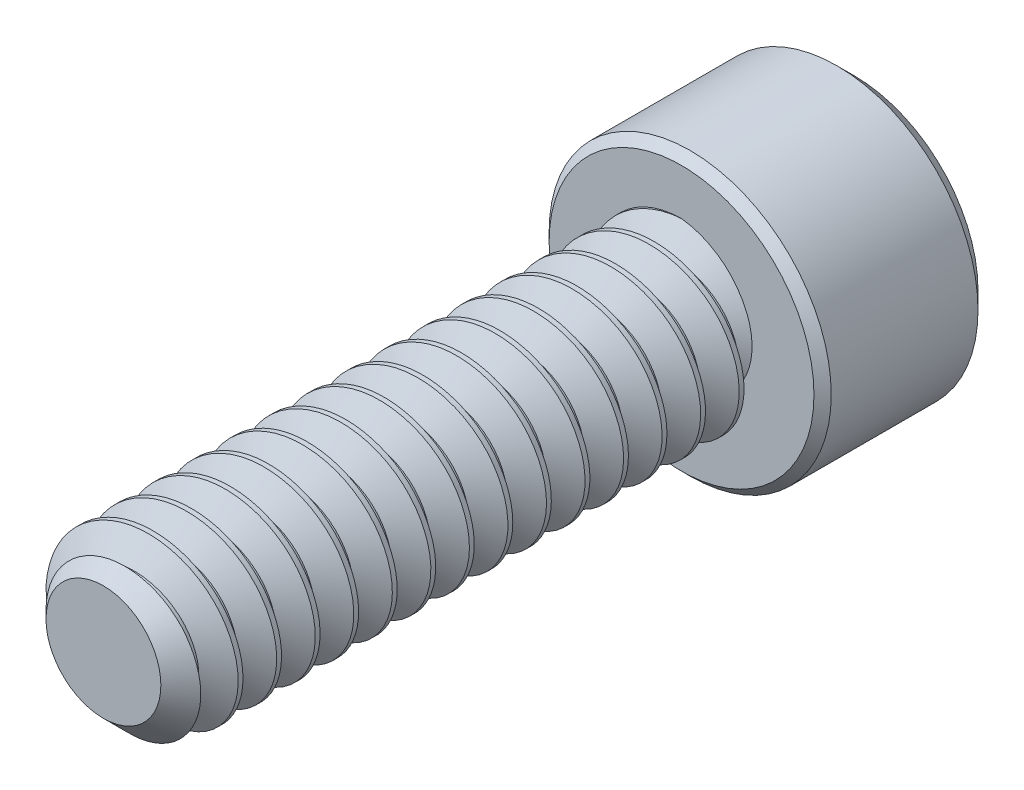
SolidWorks part; units mm, degrees
material "Plain Carbon Steel"
ref_plane "Front Plane" through (0, 0, 0) normal (0, 0, 1) x (1, 0, 0)
ref_plane "Top Plane" through (0, 0, 0) normal (0, 1, 0) x (1, 0, 0)
ref_plane "Right Plane" through (0, 0, 0) normal (1, 0, 0) x (0, 0, -1)
sketch "Sketch1" plane through (0, 0, 0) normal (0, 0, 1) x (1, 0, 0)
  line L0 (0, 1.4224) -> (0, -1.4224) construction
  circle A0 centre (0, 0) radius 1.4224
  dimension "OD" = 2.8448
extrude "Extrude1" add sketch "Sketch1" against normal blind 9.525
sketch "Sketch2" plane through (0, 0, 0) normal (0, 0, 1) x (1, 0, 0)
  circle A0 centre (0, 0) radius 1.4224 construction
  circle A1 centre (0, 0) radius 1.4224
curve "Helix/Spiral1" pitch 0.635 height 10.16 radius 1.4224 centre (0, 0, 0) axis (0, 0, -1) start towards (0, 1, 0) parameters "pitch"=0.635
chamfer "Chamfer3" distance 0.4763 angle 45 1 edges at (1.4224, 0, 0)
sketch "Sketch3" plane through (0, 0, 0) normal (1, 0, 0) x (0, 0, -1)
  line L0 (-0.5556, 1.4224) -> (-0.3175, 1.01)
  line L1 (-0.3175, 1.01) -> (-0.2381, 1.01)
  line L2 (-0.2381, 1.01) -> (0, 1.4224)
  line L3 (-0.5556, 1.4224) -> (0, 1.4224)
  line L4 (-0.2778, 1.4224) -> (-0.2778, 1.01) construction
  line L5 (-0.4366, 1.2162) -> (-0.1191, 1.2162) construction
  line L6 (0, 1.4224) -> (0, -1.4224) construction
  dimension "D1" = 0.0794
  dimension "D2" = 0.3175
  dimension "D3" = 60
sweep "Cut-Sweep1" cut profiles "Sketch3" path "Helix/Spiral1" align with end faces yes
sketch "Sketch6" plane through (0, 0, -9.525) normal (0, 0, -1) x (-1, 0, 0)
  circle A0 centre (0, 0) radius 2.3241
  dimension "head dia" = 4.6482
extrude "Extrude2" add sketch "Sketch6" along normal blind 2.8448
sketch "Sketch7" plane through (0, 0, -12.3698) normal (0, 0, -1) x (-1, 0, 0)
  line L1 (0, 1.3748) -> (-1.1906, 0.6874)
  line L2 (-1.1906, 0.6874) -> (-1.1906, -0.6874)
  line L3 (-1.1906, -0.6874) -> (0, -1.3748)
  line L4 (0, -1.3748) -> (1.1906, -0.6874)
  line L5 (1.1906, -0.6874) -> (1.1906, 0.6874)
  line L6 (1.1906, 0.6874) -> (0, 1.3748)
  circle A0 centre (0, 0) radius 1.1906 construction
  dimension "hex dia" = 2.3813
extrude "Cut-Extrude1" cut sketch "Sketch7" against normal blind 1.7859
sketch "Sketch8" plane through (0, 0, -12.3698) normal (0, 0, -1) x (-1, 0, 0)
  circle A0 centre (0, 0) radius 1.3748
extrude "Cut-Extrude2" cut sketch "Sketch8" against normal blind 0.2845 draft 45
chamfer "Chamfer1" distance 0.2845 angle 45 1 edges at (-2.3241, 0, -12.3698)
chamfer "Chamfer2" distance 0.1422 angle 45 1 edges at (-2.3241, 0, -9.525)
sketch "Sketch9" plane through (0, 0, 0) normal (1, 0, 0) x (0, 0, -1)
  line L0 (0, 1.4224) -> (0, -1.4224) construction
  line L1 (3.4925, 1.4224) -> (3.4925, -1.4224) construction
  line L2 (9.525, 2.3241) -> (9.525, -2.3241) construction
  line L3 (12.3698, 2.3241) -> (12.3698, -2.3241) construction
  line L4 (12.3698, 0) -> (0, 0) construction
  dimension "D1" = 3.4925
  dimension "D2" = 2.8448
  dimension "D3" = 4.6482
  dimension "D4" = 9.525
equation "\"D3@Helix/Spiral1\" = \"screw length@Extrude1\"+\"pitch@Helix/Spiral1\""
equation "\"D1@Sketch3\" = \"pitch@Helix/Spiral1\"*.125"
equation "\"D2@Sketch3\" = \"pitch@Helix/Spiral1\"*.5"
equation "\"D1@Cut-Extrude1\" = \"hex dia@Sketch7\"*.75"
equation "\"D1@Chamfer1\" = \"head depth@Extrude2\"/10"
equation "\"D1@Sketch9\" = \"pitch@Helix/Spiral1\"*5.5"
equation "\"D1@Chamfer2\" = \"D1@Chamfer1\"/2"
equation "\"D1@Cut-Extrude2\" = \"D1@Chamfer2\"*2"
equation "\"D1@Chamfer3\" = \"pitch@Helix/Spiral1\"*.750"
equation "\"D2@Sketch9\" = \"head depth@Extrude2\""
equation "\"D3@Sketch9\" = \"head dia@Sketch6\""
equation "\"D4@Sketch9\" = \"screw length@Extrude1\""
